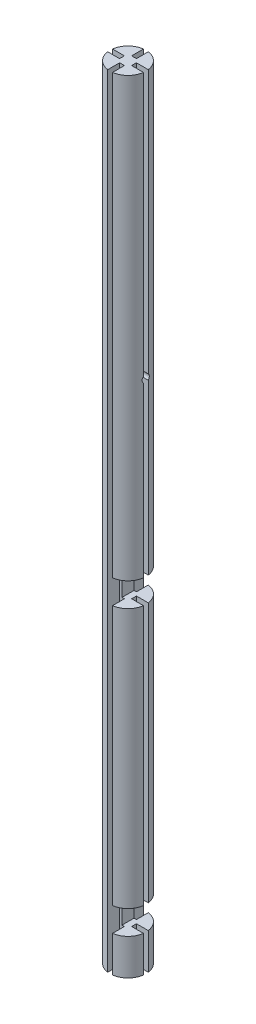
SolidWorks part; units mm, degrees
ref_plane "Front Plane" through (0, 0, 0) normal (0, 0, 1) x (1, 0, 0)
ref_plane "Top Plane" through (0, 0, 0) normal (0, 1, 0) x (1, 0, 0)
ref_plane "Right Plane" through (0, 0, 0) normal (1, 0, 0) x (0, 0, -1)
sketch "Sketch1" plane through (0, 0, 0) normal (0, 1, 0) x (1, 0, 0)
  line L5 (0, 194.8226) -> (0, 75) construction
  line L18 (-10, 74.3303) -> (-10, 25)
  line L19 (-10, 25) -> (10, 25)
  line L20 (10, 74.3303) -> (10, 25)
  line L21 (-29.2048, 0) -> (25.2155, 0) construction
  line L22 (74.3303, -10) -> (25, -10)
  line L23 (74.3303, 10) -> (25, 10)
  line L24 (25, 10) -> (25, -10)
  line L25 (-10, -74.3303) -> (-10, -25)
  line L26 (10, -74.3303) -> (10, -25)
  line L27 (10, -25) -> (-10, -25)
  line L28 (-74.3303, 10) -> (-25, 10)
  line L29 (-74.3303, -10) -> (-25, -10)
  line L30 (-25, -10) -> (-25, 10)
  line L31 (0, 75) -> (0, 25) construction
  line L32 (0, 25) -> (0, -243.8201) construction
  arc A2 (-10, 74.3303) -> (-74.3303, 10) centre (0, 0) ccw
  arc A3 (-74.3303, -10) -> (-10, -74.3303) centre (0, 0) ccw
  arc A4 (10, -74.3303) -> (74.3303, -10) centre (0, 0) ccw
  arc A5 (74.3303, 10) -> (10, 74.3303) centre (0, 0) ccw
  arc A6 (-10, 74.3303) -> (29.2889, 69.0446) centre (0, 0) cw
  point P1 (0, 25)
  point P4 (0, 93.7498)
  point P24 (-100, 0)
  point P29 (0, 0)
  point P30 (0, 0)
  dimension "D1" = 150
  dimension "D2" = 20
  dimension "D3" = 50
  dimension "D4" = 4
extrude "Boss-Extrude2" add sketch "Sketch1" along normal blind 4000 contours A2 L28 L30 L29 A3 L25 L27 L26 A4 L22 L24 L23 A5 L20 L19 L18
sketch "Sketch2" plane through (0, 0, 0) normal (0, 1, 0) x (1, 0, 0)
  line L0 (0, 74.3303) -> (0, -76.7183)
  line L1 (74.3303, 74.3303) -> (74.3303, -76.7183)
  line L2 (74.3303, 74.3303) -> (0, 74.3303)
  line L3 (74.3303, -76.7183) -> (0, -76.7183)
extrude "Cut-Extrude1" cut sketch "Sketch2" along normal mid plane 100 from offset 200
extrude "Cut-Extrude2" cut sketch "Sketch2<2>" against normal mid plane 100 from offset 1380
sketch "Sketch2<2>" plane through (0, 0, 0) normal (0, 1, 0) x (1, 0, 0) same geometry as "Sketch2"
ref_plane "Plane1" through (74.3303, 0, 0) normal (1, 0, 0) x (0, 0, -1)
ref_plane "Plane2" through (0, 0, -74.3303) normal (0, 0, -1) x (-1, 0, 0)
sketch "Sketch3" plane through (74.3303, 0, 0) normal (1, 0, 0) x (0, 0, -1)
  circle A0 centre (0, 2143) radius 15.2
extrude "Cut-Extrude3" cut sketch "Sketch3" against normal up to surface (49.3303 mm away) up to face at (25, 790, 0)
sketch "Sketch4" plane through (0, 0, -74.3303) normal (0, 0, -1) x (-1, 0, 0)
  circle A2 centre (0, 2143) radius 15.2
extrude "Cut-Extrude4" cut sketch "Sketch4" against normal up to surface (49.3303 mm away) up to face at (3.3333, 1193.3333, -25)
sketch "Sketch5" plane through (0, 0, 25) normal (0, 0, 1) x (1, 0, 0)
  line L0 (-74.3303, 4000) -> (-74.3303, 3250)
  line L9 (-74.3303, 4000) -> (-74.3303, 0) construction
  line L10 (-74.3303, 3250) -> (74.3303, 3250)
  line L11 (74.3303, -16.72) -> (74.3303, 16.72) construction
  line L12 (74.3303, 3250) -> (74.3303, 4000)
  line L13 (74.3303, 4000) -> (74.3303, 2154.4473) construction
  line L14 (-74.3303, 4000) -> (74.3303, 4000)
extrude "Cut-Extrude5" cut sketch "Sketch5" against normal through all both and the other way through all
sketch "Sketch7" plane through (0, 1330, 0) normal (0, 1, 0) x (1, 0, 0)
  line L0 (0, 25) -> (10, 25)
  line L1 (-10, 25) -> (10, 25) construction
  line L2 (10, 25) -> (10, 74.3303)
  line L3 (16.72, 74.3303) -> (-16.72, 74.3303) construction
  line L4 (10, 74.3303) -> (10, 25) construction
  line L5 (0, -25) -> (10, -25)
  line L6 (10, -25) -> (-10, -25) construction
  line L7 (10, -25) -> (10, -74.3303)
  line L8 (25, -10) -> (74.3303, -10)
  line L9 (74.3303, 10) -> (25, 10)
  line L10 (25, 10) -> (25, -10)
  line L11 (0, 25) -> (0, -25)
  arc A0 (10, -74.3303) -> (10, 74.3303) centre (0, 0) ccw
